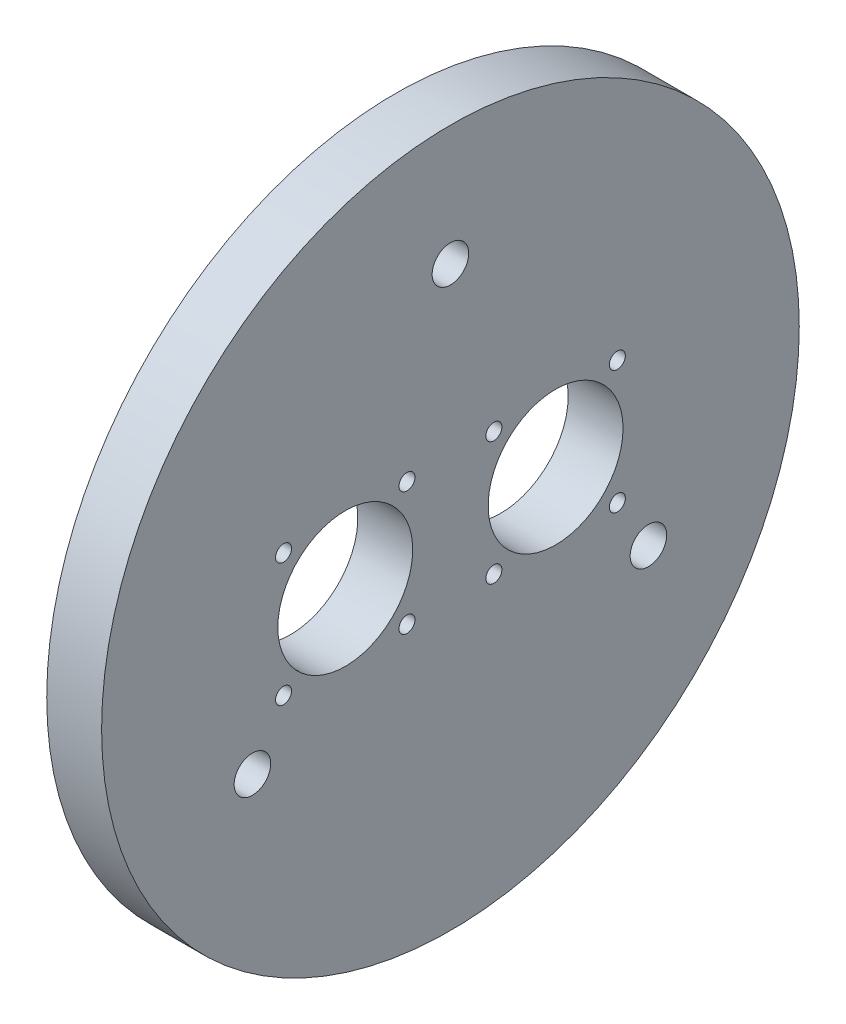
SolidWorks part; units mm, degrees
ref_plane "Front Plane" through (0, 0, 0) normal (0, 0, 1) x (1, 0, 0)
ref_plane "Top Plane" through (0, 0, 0) normal (0, 1, 0) x (1, 0, 0)
ref_plane "Right Plane" through (0, 0, 0) normal (1, 0, 0) x (0, 0, -1)
sketch "Sketch1" plane through (0, 0, 0) normal (1, 0, 0) x (0, 0, -1)
  line L0 (0, -76.29) -> (0, 76.29) construction
  line L1 (-76.29, 0) -> (76.29, 0) construction
  line L2 (23, 0) -> (36.4969, 13.4969) construction
  circle A0 centre (0, 0) radius 76.29
  circle A1 centre (0, 50) radius 4
  circle A2 centre (43.3013, -25) radius 4
  circle A3 centre (-43.3013, -25) radius 4
  circle A4 centre (23, 0) radius 14.75
  circle A5 centre (-23, 0) radius 14.75
  circle A6 centre (36.4969, 13.4969) radius 1.75
  circle A7 centre (36.4969, -13.4969) radius 1.75
  circle A8 centre (9.5031, -13.4969) radius 1.75
  circle A9 centre (9.5031, 13.4969) radius 1.75
  circle A10 centre (-36.4969, -13.4969) radius 1.75
  circle A11 centre (-9.5031, -13.4969) radius 1.75
  circle A12 centre (-9.5031, 13.4969) radius 1.75
  circle A13 centre (-36.4969, 13.4969) radius 1.75
  point P12 (0, 0)
  point P29 (23, 0)
  dimension "D1" = 152.58
  dimension "D2" = 8
  dimension "D5" = 29.5
  dimension "D7" = 3.5
  dimension "D3" = 50
  dimension "D4" = 3
  dimension "D6" = 23
  dimension "D8" = 19.0875
  dimension "D10" = 45
  dimension "D9" = 4
extrude "Boss-Extrude1" add sketch "Sketch1" along normal blind 12
